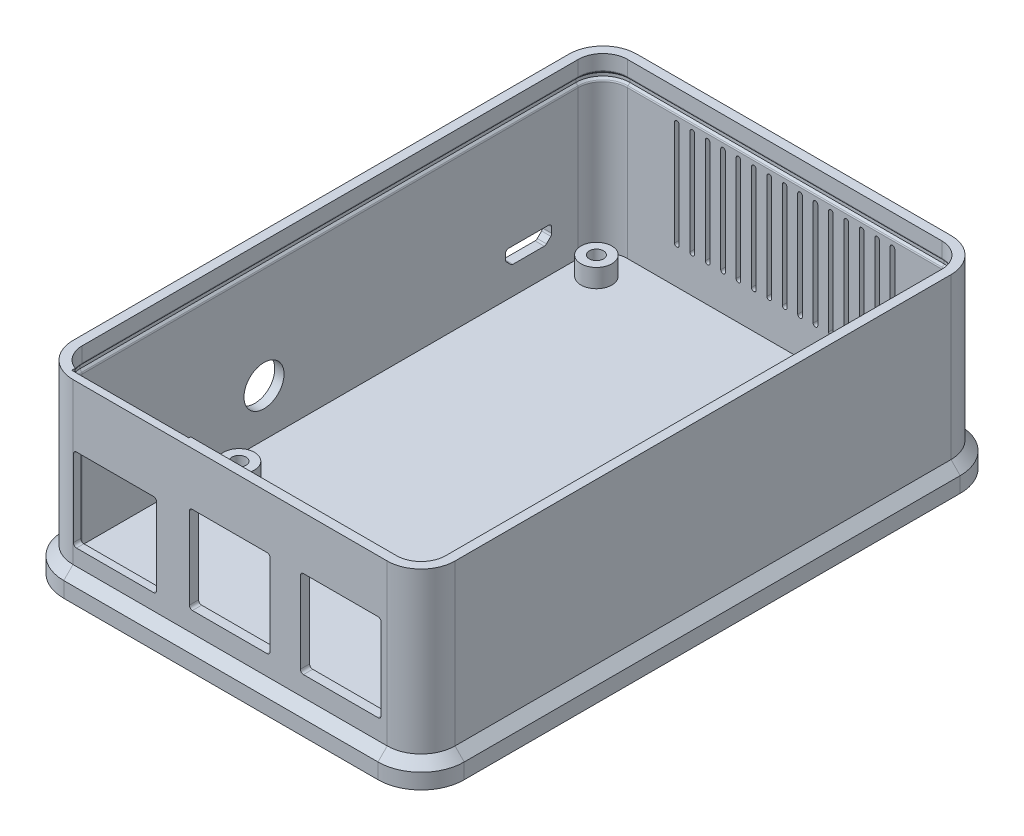
SolidWorks part; units mm, degrees
ref_plane "Front Plane" through (0, 0, 0) normal (0, 0, 1) x (1, 0, 0)
ref_plane "Top Plane" through (0, 0, 0) normal (0, 1, 0) x (1, 0, 0)
ref_plane "Right Plane" through (0, 0, 0) normal (1, 0, 0) x (0, 0, -1)
sketch "Sketch1" plane through (0, 0, 0) normal (0, 1, 0) x (1, 0, 0)
  line L0 (-29, 40) -> (-29, -40.5)
  line L1 (-23.5, 44) -> (27.5, 44)
  line L2 (-27.5, 40) -> (-27.5, -40.5)
  line L3 (-23.5, -44.5) -> (27.5, -44.5)
  line L4 (31.5, 40) -> (31.5, -40.5)
  line L5 (-23.5, -46) -> (27.5, -46)
  line L6 (33, 40) -> (33, -40.5)
  line L7 (-23.5, 45.5) -> (27.5, 45.5)
  arc A0 (-27.5, -40.5) -> (-23.5, -44.5) centre (-23.5, -40.5) ccw
  arc A1 (27.5, -44.5) -> (31.5, -40.5) centre (27.5, -40.5) ccw
  arc A2 (27.5, 44) -> (31.5, 40) centre (27.5, 40) cw
  arc A3 (-23.5, 44) -> (-27.5, 40) centre (-23.5, 40) ccw
  arc A4 (-29, -40.5) -> (-23.5, -46) centre (-23.5, -40.5) ccw
  arc A5 (27.5, -46) -> (33, -40.5) centre (27.5, -40.5) ccw
  arc A6 (27.5, 45.5) -> (33, 40) centre (27.5, 40) cw
  arc A7 (-23.5, 45.5) -> (-29, 40) centre (-23.5, 40) ccw
  point P7 (-27.5, -44.5)
  point P14 (-27.5, 44)
  dimension "D7" = 4
  dimension "D1" = 27.5
  dimension "D2" = 44.5
  dimension "D3" = 88.5
  dimension "D4" = 59
  dimension "D5" = 31.5
  dimension "D6" = 44
  dimension "D8" = 1.5
extrude "Boss-Extrude1" add sketch "Sketch1" along normal blind 25 and the other way blind 3
sketch "Sketch2" plane through (0, -3, 0) normal (0, -1, 0) x (1, 0, 0)
  line L4 (-23.5, -45.5) -> (27.5, -45.5)
  line L5 (33, -40) -> (33, 40.5)
  line L6 (27.5, 46) -> (-23.5, 46)
  line L7 (-29, 40.5) -> (-29, -40)
  line L8 (-23.5, -45.5) -> (27.5, -45.5)
  line L9 (33, -40) -> (33, 40.5)
  line L10 (27.5, 46) -> (-23.5, 46)
  line L11 (-29, 40.5) -> (-29, -40)
  arc A4 (-29, -40) -> (-23.5, -45.5) centre (-23.5, -40) ccw
  arc A5 (27.5, -45.5) -> (33, -40) centre (27.5, -40) ccw
  arc A6 (33, 40.5) -> (27.5, 46) centre (27.5, 40.5) ccw
  arc A7 (-23.5, 46) -> (-29, 40.5) centre (-23.5, 40.5) ccw
  arc A8 (-29, -40) -> (-23.5, -45.5) centre (-23.5, -40) ccw
  arc A9 (27.5, -45.5) -> (33, -40) centre (27.5, -40) ccw
  arc A10 (33, 40.5) -> (27.5, 46) centre (27.5, 40.5) ccw
  arc A11 (-23.5, 46) -> (-29, 40.5) centre (-23.5, 40.5) ccw
  dimension "D1" = 0
extrude "Boss-Extrude2" add sketch "Sketch2" along normal blind 2
sketch "Sketch7" plane through (-29, 0, 0) normal (-1, 0, 0) x (0, 0, 1)
  line L0 (0, -13.75) -> (0, 13.75) construction
  line L1 (-35.7, 4.1) -> (-35.7, 2.5)
  line L2 (35.75, 0) -> (-35.75, 0) construction
  line L3 (-35.7, 4.1) -> (-28.2, 4.1)
  line L4 (-35.7, 2.5) -> (-34.7, 1.5)
  line L5 (-34.7, 1.5) -> (-29.2, 1.5)
  line L6 (-29.2, 1.5) -> (-28.2, 2.5)
  line L7 (-28.2, 2.5) -> (-28.2, 4.1)
  circle A0 centre (11, 4.65) radius 3.25
  dimension "D1" = 6.5
  dimension "D2" = 11
  dimension "D3" = 4.65
  dimension "D4" = 45
  dimension "D5" = 45
  dimension "D6" = 7.5
  dimension "D7" = 2.6
  dimension "D8" = 5.5
  dimension "D9" = 28.2
  dimension "D10" = 1.5
extrude "Cut-Extrude1" cut sketch "Sketch7" against normal up to surface (1.5 mm away) up to face at (-27.5, 11, 0.25)
fillet "Fillet1" radius 0.5 6 edges at (-28.25, 4.1, -28.2) (-28.25, 2.5, -28.2) (-28.25, 1.5, -29.2) (-28.25, 1.5, -34.7) (-28.25, 2.5, -35.7) (-28.25, 4.1, -35.7)
sketch "Sketch8" plane through (0, 0, 46) normal (0, 0, 1) x (1, 0, 0)
  line L0 (35.75, 0) -> (-35.75, 0) construction
  line L1 (13.4, 16.43) -> (26.5, 16.43)
  line L2 (13.4, 16.43) -> (13.4, 2.23)
  line L3 (13.4, 2.23) -> (26.5, 2.23)
  line L4 (26.5, 16.43) -> (26.5, 2.23)
  line L5 (8.48, 16.43) -> (-4.62, 16.43)
  line L6 (8.48, 16.43) -> (8.48, 2.23)
  line L7 (8.48, 2.23) -> (-4.62, 2.23)
  line L8 (-4.62, 16.43) -> (-4.62, 2.23)
  line L9 (-23.44, 15.1) -> (-9.94, 15.1)
  line L10 (-23.44, 15.1) -> (-23.44, 1.6)
  line L11 (-23.44, 1.6) -> (-9.94, 1.6)
  line L12 (-9.94, 15.1) -> (-9.94, 1.6)
  line L13 (0, -13.75) -> (0, 13.75) construction
  dimension "D1" = 13.1
  dimension "D2" = 14.2
  dimension "D3" = 13.1
  dimension "D4" = 14.2
  dimension "D5" = 2.23
  dimension "D6" = 4.62
  dimension "D7" = 13.4
  dimension "D8" = 13.5
  dimension "D9" = 23.44
  dimension "D10" = 1.6
  dimension "D11" = 13.5
extrude "Cut-Extrude2" cut sketch "Sketch8" against normal up to surface (1.5 mm away) up to face at (2, 11, 44.5)
fillet "Fillet2" radius 0.5 12 edges at (-9.94, 15.1, 45.25) (-23.44, 15.1, 45.25) (-23.44, 1.6, 45.25) (-9.94, 1.6, 45.25) (-4.62, 2.23, 45.25) (-4.62, 16.43, 45.25) (8.48, 2.23, 45.25) (8.48, 16.43, 45.25) (26.5, 16.43, 45.25) (13.4, 16.43, 45.25) (13.4, 2.23, 45.25) (26.5, 2.23, 45.25)
sketch "Sketch9" plane through (0, -3, 0) normal (0, 1, 0) x (1, 0, 0)
  line L0 (-24.9, -44.8) -> (-5.9, -44.8)
  line L1 (-24.9, -44.8) -> (-24.9, -44.247)
  line L2 (-5.9, -44.8) -> (-5.9, -44.5)
  line L3 (-23.5, -44.5) -> (27.5, -44.5) construction
  line L4 (-5.9, -44.5) -> (-23.5, -44.5)
  line L5 (-23.5, -44.5) -> (27.5, -44.5) construction
  arc A0 (-27.5, -40.5) -> (-23.5, -44.5) centre (-23.5, -40.5) ccw construction
  arc A1 (-24.9, -44.247) -> (-23.5, -44.5) centre (-23.5, -40.5) ccw
  dimension "D1" = 1.4
  dimension "D2" = 19
  dimension "D3" = 0.3
extrude "Cut-Extrude3" cut sketch "Sketch9" along normal through all
sketch "Sketch10" plane through (0, -3, 0) normal (0, 1, 0) x (1, 0, 0)
  line L0 (0, -13.75) -> (0, 13.75) construction
  line L1 (-13.75, 0) -> (13.75, 0) construction
  circle A0 centre (-23.5517, 39) radius 2.5
  circle A1 centre (25.4483, 39) radius 2.5
  circle A2 centre (25.4483, -19) radius 2.5
  circle A3 centre (-23.5517, -19) radius 2.5
  circle A4 centre (-23.5517, 39) radius 1.15
  circle A5 centre (25.4483, 39) radius 1.15
  circle A6 centre (-23.5517, -19) radius 1.15
  circle A7 centre (25.4483, -19) radius 1.15
  dimension "D1" = 49
  dimension "D2" = 58
  dimension "D3" = 5
  dimension "D6" = 2.3
  dimension "D4" = 23.5517
  dimension "D5" = 39
extrude "Boss-Extrude4" add sketch "Sketch10" along normal blind 3
sketch "Sketch15" plane through (0, -5, 0) normal (0, -1, 0) x (1, 0, 0)
  line L0 (-30.5, 40.5) -> (-30.5, -40)
  line L1 (-23.5, -47) -> (27.5, -47)
  line L2 (34.5, -40) -> (34.5, 40.5)
  line L3 (27.5, 47.5) -> (-23.5, 47.5)
  line L4 (-23.5, -45.5) -> (27.5, -45.5)
  line L5 (33, -40) -> (33, 40.5)
  line L6 (27.5, 46) -> (-23.5, 46)
  line L7 (-29, 40.5) -> (-29, -40)
  line L8 (-23.5, -45.5) -> (27.5, -45.5)
  line L9 (33, -40) -> (33, 40.5)
  line L10 (27.5, 46) -> (-23.5, 46)
  line L11 (-29, 40.5) -> (-29, -40)
  arc A0 (-30.5, -40) -> (-23.5, -47) centre (-23.5, -40) ccw
  arc A1 (27.5, -47) -> (34.5, -40) centre (27.5, -40) ccw
  arc A2 (34.5, 40.5) -> (27.5, 47.5) centre (27.5, 40.5) ccw
  arc A3 (-23.5, 47.5) -> (-30.5, 40.5) centre (-23.5, 40.5) ccw
  arc A4 (-29, -40) -> (-23.5, -45.5) centre (-23.5, -40) ccw
  arc A5 (27.5, -45.5) -> (33, -40) centre (27.5, -40) ccw
  arc A6 (33, 40.5) -> (27.5, 46) centre (27.5, 40.5) ccw
  arc A7 (-23.5, 46) -> (-29, 40.5) centre (-23.5, 40.5) ccw
  arc A8 (-29, -40) -> (-23.5, -45.5) centre (-23.5, -40) ccw
  arc A9 (27.5, -45.5) -> (33, -40) centre (27.5, -40) ccw
  arc A10 (33, 40.5) -> (27.5, 46) centre (27.5, 40.5) ccw
  arc A11 (-23.5, 46) -> (-29, 40.5) centre (-23.5, 40.5) ccw
  dimension "D1" = 0
  dimension "D2" = 1.5
extrude "Boss-Extrude7" add sketch "Sketch15" against normal blind 4
chamfer "Chamfer2" distance 1.5 angle 45 8 edges at (34.5, -1, 0.25) (32.4497, -1, 45.4497) (32.4497, -1, -44.9497) (2, -1, 47.5) (2, -1, -47) (-28.4497, -1, 45.4497) (-28.4497, -1, -44.9497) (-30.5, -1, 0.25)
sketch "Sketch17" plane through (0, 0, 0) normal (0, 0, 1) x (1, 0, 0)
  line L0 (-27.5, 22.45) -> (-27.9, 22.05)
  line L1 (-27.5, -3) -> (-27.5, 25) construction
  line L2 (-27.9, 22.05) -> (-27.9, 21.55)
  line L3 (-27.9, 21.55) -> (-27.5, 21.15)
  line L4 (-27.5, 21.15) -> (-27.5, 22.45)
  line L7 (35.75, 0) -> (-35.75, 0) construction
  dimension "D1" = 0.4
  dimension "D2" = 1.3
  dimension "D3" = 22.45
ref_plane "Plane1" through (0, 21.55, 0) normal (0, 1, 0) x (1, 0, 0)
sketch "Sketch18" plane through (0, 21.55, 0) normal (0, 1, 0) x (1, 0, 0)
  line L0 (-27.5, 40) -> (-27.5, -40.5) construction
  line L1 (27.5, 44) -> (-23.5, 44) construction
  line L2 (31.5, -40.5) -> (31.5, 40) construction
  line L3 (-5.9, -44.5) -> (27.5, -44.5) construction
  line L4 (-27.5, 40) -> (-27.5, -40.5)
  line L5 (27.5, 44) -> (-23.5, 44)
  line L6 (31.5, -40.5) -> (31.5, 40)
  line L7 (-23.5, -44.5) -> (27.5, -44.5)
  arc A0 (-23.5, 44) -> (-27.5, 40) centre (-23.5, 40) ccw construction
  arc A1 (31.5, 40) -> (27.5, 44) centre (27.5, 40) ccw construction
  arc A2 (27.5, -44.5) -> (31.5, -40.5) centre (27.5, -40.5) ccw construction
  arc A3 (-27.5, -40.5) -> (-24.9, -44.247) centre (-23.5, -40.5) ccw construction
  arc A4 (-23.5, 44) -> (-27.5, 40) centre (-23.5, 40) ccw
  arc A5 (31.5, 40) -> (27.5, 44) centre (27.5, 40) ccw
  arc A6 (27.5, -44.5) -> (31.5, -40.5) centre (27.5, -40.5) ccw
  arc A7 (-27.5, -40.5) -> (-23.5, -44.5) centre (-23.5, -40.5) ccw
sweep "Cut-Sweep1" cut profiles "Sketch17" path "Sketch18"
fillet "Fillet3" radius 0.3 16 edges at (10.8, 21.15, 44.5) (30.3284, 21.15, 43.3284) (31.5, 21.15, 0.25) (30.3284, 21.15, -42.8284) (2, 21.15, -44) (-26.3284, 21.15, -42.8284) (-26.7863, 21.15, 42.7804) (10.8, 22.45, 44.5) (30.3284, 22.45, 43.3284) (31.5, 22.45, 0.25) (30.3284, 22.45, -42.8284) (2, 22.45, -44) (-26.3284, 22.45, -42.8284) (-26.7863, 22.45, 42.7804)
sketch "Sketch19" plane through (0, 0, -45.5) normal (0, 0, -1) x (-1, 0, 0)
  line L0 (-2, 20) -> (-2, 3) construction
  line L1 (-1.625, 20) -> (-1.625, 3)
  line L2 (-2.375, 20) -> (-2.375, 3)
  line L6 (-27.5, -1) -> (-27.5, 25) construction
  line L7 (23.5, -1) -> (23.5, 25) construction
  line L8 (-27.5, -1) -> (-27.5, 25) construction
  line L9 (23.5, -1) -> (23.5, 25) construction
  arc A0 (-1.625, 20) -> (-2.375, 20) centre (-2, 20) ccw
  arc A1 (-2.375, 3) -> (-1.625, 3) centre (-2, 3) ccw
  point P2 (-2, 11.5)
  point P9 (0, 0)
  dimension "D1" = 0.75
  dimension "D2" = 11.5
  dimension "D3" = 25.5
  dimension "D4" = 25.5
  dimension "D5" = 17
extrude "Cut-Extrude4" cut sketch "Sketch19" against normal up to surface (1.5 mm away) up to face at (2, 9.0129, -44)
pattern_linear "LPattern1" count 8 spacing 2.5 along (-1, 0, 0) count 8 spacing 2.5 along (1, 0, 0) of "Cut-Extrude4"
